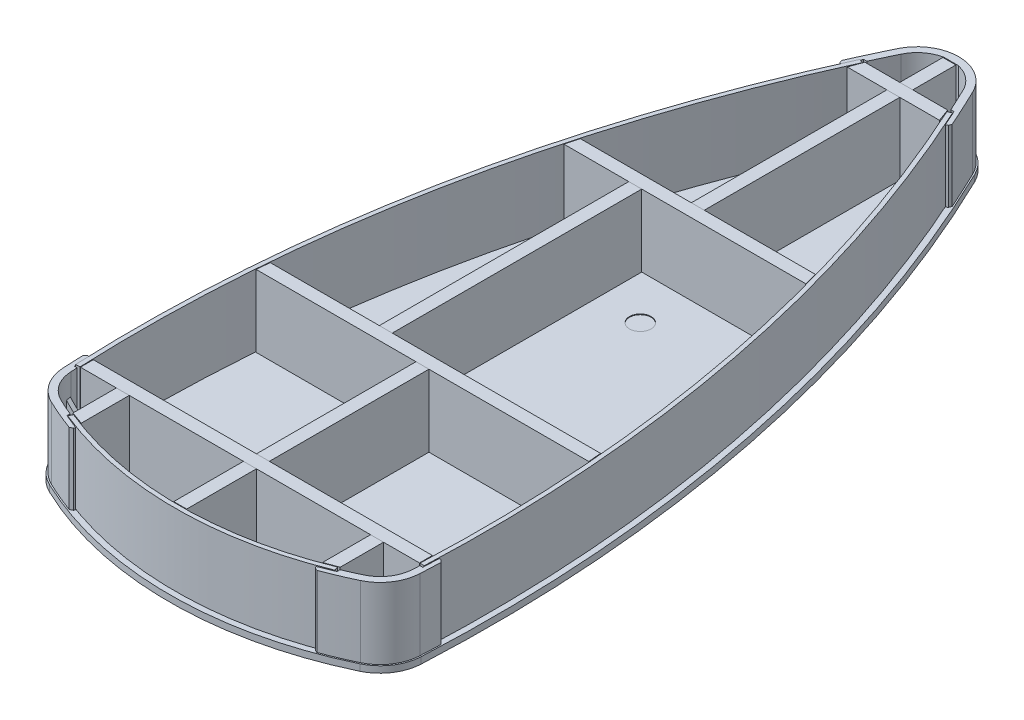
SolidWorks part; units mm, degrees
ref_plane "Front Plane" through (0, 0, 0) normal (0, 0, 1) x (1, 0, 0)
ref_plane "Top Plane" through (0, 0, 0) normal (0, 1, 0) x (1, 0, 0)
ref_plane "Right Plane" through (0, 0, 0) normal (1, 0, 0) x (0, 0, -1)
sketch "Sketch1" plane through (0, 0, 0) normal (0, 1, 0) x (1, 0, 0)
  line L0 (0, 550) -> (0, -550) construction
  arc A0 (-54.0521, 516.0455) -> (54.0521, 516.0455) centre (0, 490) cw
  arc A1 (-54.0521, 516.0455) -> (-249.9284, -449.7924) centre (1747.686, -352.1364) ccw
  arc A2 (-249.9284, -449.7924) -> (-215.9091, -500.9803) centre (-190, -446.8627) ccw
  arc A3 (-215.9091, -500.9803) -> (215.9091, -500.9803) centre (0, -50) ccw
  arc A4 (249.9284, -449.7924) -> (215.9091, -500.9803) centre (190, -446.8627) cw
  arc A5 (54.0521, 516.0455) -> (249.9284, -449.7924) centre (-1747.686, -352.1364) cw
  dimension "D1" = 500
  dimension "D2" = 500
  dimension "D4" = 2000
  dimension "D5" = 60
  dimension "D3" = 1100
extrude "Boss-Extrude1" add sketch "Sketch1" against normal blind 9
sketch "Sketch2" plane through (0, 0, 0) normal (0, 1, 0) x (1, 0, 0)
  line L0 (0, -120) -> (0, 105) construction
  circle A0 centre (0, 105) radius 15
  circle A1 centre (0, -120) radius 15
  dimension "D2" = 30
  dimension "D1" = 225
  dimension "D3" = 120
extrude "Cut-Extrude1" cut sketch "Sketch2" against normal blind 1
sketch "Sketch3" plane through (0, 0, 0) normal (0, 1, 0) x (1, 0, 0)
  line L0 (0, 475) -> (0, 0) construction
  line L1 (-9, 535) -> (9, 535)
  line L2 (-9, 535) -> (-9, 475)
  line L3 (-9, 475) -> (9, 475)
  line L4 (9, 535) -> (9, 475)
  line L5 (0, 550) -> (0, 535) construction
  arc A1 (54.0521, 516.0455) -> (-54.0521, 516.0455) centre (0, 490) ccw construction
  dimension "D1" = 18
  dimension "D2" = 15
  dimension "D3" = 60
extrude "Boss-Extrude2" add sketch "Sketch3" along normal blind 100 separate body
sketch "Sketch4" plane through (0, 0, 0) normal (0, 1, 0) x (1, 0, 0)
  line L0 (0, -180) -> (0, -198) construction
  line L1 (-57.642, 475) -> (57.642, 475)
  line L2 (-57.642, 475) -> (-64.1934, 457)
  line L3 (-64.1934, 457) -> (64.1934, 457)
  line L4 (57.642, 475) -> (64.1934, 457)
  line L5 (-9, 475) -> (9, 475) construction
  line L6 (0, 475) -> (0, 457) construction
  line L7 (9, 535) -> (-9, 535) construction
  line L8 (0, 535) -> (0, 550) construction
  line L9 (60.9177, 466) -> (75.0131, 471.1303) construction
  line L10 (0, 9) -> (0, 457) construction
  line L11 (-229.8118, -180) -> (229.8118, -180)
  line L12 (-229.8118, -180) -> (-231.3866, -198)
  line L13 (-231.3866, -198) -> (231.3866, -198)
  line L14 (229.8118, -180) -> (231.3866, -198)
  line L15 (230.5992, -189) -> (245.5421, -187.6927) construction
  line L16 (0, 9) -> (0, -9) construction
  line L17 (0, -550) -> (0, -493.7862) construction
  line L18 (0, -438) -> (0, -420) construction
  line L19 (-235.8365, -420) -> (235.8365, -420)
  line L20 (-235.8365, -420) -> (-235.8365, -438)
  line L21 (-235.8365, -438) -> (235.8365, -438)
  line L22 (235.8365, -420) -> (235.8365, -438)
  line L23 (0, -420) -> (0, 0) construction
  line L24 (235.8365, -429) -> (250.8365, -429) construction
  line L25 (0, 185) -> (0, 167) construction
  line L26 (-163.3545, 185) -> (163.3545, 185)
  line L27 (-163.3545, 185) -> (-168.1776, 167)
  line L28 (-168.1776, 167) -> (168.1776, 167)
  line L29 (163.3545, 185) -> (168.1776, 167)
  line L30 (165.766, 176) -> (180.2549, 179.8823) construction
  arc A0 (54.0521, 516.0455) -> (-54.0521, 516.0455) centre (0, 490) ccw construction
  arc A1 (249.9284, -449.7924) -> (54.0521, 516.0455) centre (-1747.686, -352.1364) ccw construction
  arc A2 (-215.9091, -500.9803) -> (215.9091, -500.9803) centre (0, -50) ccw construction
  dimension "D1" = 70
  dimension "D2" = 85
  dimension "D3" = 420
  dimension "D4" = 240
  dimension "D5" = 105
  dimension "D6" = 290
extrude "Boss-Extrude3" add sketch "Sketch4" along normal up to surface (100 mm away) separate body up to face at (0, 100, -505)
sketch "Sketch5" plane through (0, 0, 0) normal (0, 1, 0) x (1, 0, 0)
  line L0 (-235.8365, -438) -> (235.8365, -438) construction
  line L1 (-185.8365, -438) -> (-167.8365, -438)
  line L2 (-185.8365, -438) -> (-185.8365, -498.3413)
  line L3 (-185.8365, -498.3413) -> (-167.8365, -504.8928)
  line L4 (-167.8365, -438) -> (-167.8365, -504.8928)
  line L5 (-235.8365, -420) -> (-235.8365, -438) construction
  line L6 (167.8365, -438) -> (185.8365, -438)
  line L7 (167.8365, -438) -> (167.8365, -504.8928)
  line L8 (167.8365, -504.8928) -> (185.8365, -498.3413)
  line L9 (185.8365, -438) -> (185.8365, -498.3413)
  line L10 (-185.8365, -438) -> (-235.8365, -438) construction
  line L11 (185.8365, -438) -> (235.8365, -438) construction
  line L12 (-176.8365, -501.6171) -> (-181.9668, -515.7125) construction
  line L13 (0, 535) -> (0, 550) construction
  line L14 (9, 535) -> (-9, 535) construction
  line L15 (0, -535) -> (0, -550) construction
  line L16 (-9, -438) -> (9, -438)
  line L17 (-9, -438) -> (-9, -535)
  line L18 (-9, -535) -> (9, -535)
  line L19 (9, -438) -> (9, -535)
  line L20 (-231.3866, -198) -> (231.3866, -198) construction
  line L21 (-9, -198) -> (9, -198)
  line L22 (-9, -198) -> (-9, -420)
  line L23 (-9, -420) -> (9, -420)
  line L24 (9, -198) -> (9, -420)
  line L25 (235.8365, -420) -> (-235.8365, -420) construction
  line L26 (-64.1934, 457) -> (64.1934, 457) construction
  line L27 (-9, 457) -> (9, 457)
  line L28 (-9, 457) -> (-9, 185)
  line L29 (-9, 185) -> (9, 185)
  line L30 (9, 457) -> (9, 185)
  line L31 (9, 475) -> (9, 535) construction
  line L32 (163.3545, 185) -> (-163.3545, 185) construction
  line L33 (-9, 535) -> (-9, 475) construction
  line L34 (-168.1776, 167) -> (168.1776, 167) construction
  line L35 (-78, 167) -> (-60, 167)
  line L36 (-78, 167) -> (-78, -180)
  line L37 (-78, -180) -> (-60, -180)
  line L38 (-60, 167) -> (-60, -180)
  line L39 (229.8118, -180) -> (-229.8118, -180) construction
  arc A0 (-215.9091, -500.9803) -> (215.9091, -500.9803) centre (0, -50) ccw construction
  arc A1 (54.0521, 516.0455) -> (-54.0521, 516.0455) centre (0, 490) ccw construction
  dimension "D1" = 70
  dimension "D2" = 50
  dimension "D3" = 60
extrude "Boss-Extrude4" add sketch "Sketch5" along normal up to surface (100 mm away) separate body up to face at (0, 100, 429)
sketch "Sketch6" plane through (0, 0, 0) normal (0, 1, 0) x (1, 0, 0)
  line L0 (57.642, 475) -> (-57.642, 475) construction
  line L1 (-235.8365, -438) -> (235.8365, -438) construction
  line L2 (185.8365, -498.3413) -> (185.8365, -438) construction
  line L3 (-185.8365, -438) -> (-185.8365, -498.3413) construction
  arc A12 (-46.8452, 512.5727) -> (-241.938, -449.4018) centre (1747.686, -352.1364) ccw
  arc A13 (-241.938, -449.4018) -> (-212.4545, -493.7647) centre (-190, -446.8627) ccw
  arc A14 (-212.4545, -493.7647) -> (212.4545, -493.7647) centre (0, -50) ccw
  arc A15 (212.4545, -493.7647) -> (241.938, -449.4018) centre (190, -446.8627) ccw
  arc A16 (241.938, -449.4018) -> (46.8452, 512.5727) centre (-1747.686, -352.1364) ccw
  arc A17 (46.8452, 512.5727) -> (-46.8452, 512.5727) centre (0, 490) ccw
  arc A18 (-64.47, 475) -> (-242.4626, -438) centre (1747.686, -352.1364) ccw
  arc A20 (-185.8365, -505.5533) -> (185.8365, -505.5533) centre (0, -50) ccw
  arc A22 (242.4626, -438) -> (64.47, 475) centre (-1747.686, -352.1364) ccw
  dimension "D1" = 8
extrude "Extrude-Thin1" add sketch "Sketch6" along normal up to surface (100 mm away) separate body thin contours A18 | A22 | A20 up to face at (0, 100, 429) thin type one direction reverse wall 6
sketch "Sketch7" plane through (0, 0, 0) normal (0, 1, 0) x (1, 0, 0)
  line L0 (-64.47, 475) -> (-72.6832, 456.7642)
  line L1 (-64.47, 475) -> (-59.0117, 472.5086) construction
  line L2 (-72.6832, 456.7642) -> (-78.154, 459.2282)
  line L3 (-9, 535) -> (-9, 475) construction
  line L4 (0, 535) -> (0, 548) construction
  line L5 (9, 535) -> (-9, 535) construction
  line L6 (-64.47, 475) -> (-62.8274, 478.6472)
  line L7 (11, 537) -> (-11, 537)
  line L8 (-11, 537) -> (-11, 536.7226)
  line L9 (-62.8274, 478.6472) -> (-58.3989, 478.6472)
  line L10 (62.8274, 478.6472) -> (58.3989, 478.6472)
  line L11 (11, 537) -> (11, 536.7226)
  line L12 (64.47, 475) -> (62.8274, 478.6472)
  line L13 (72.6832, 456.7642) -> (78.154, 459.2282)
  line L14 (64.47, 475) -> (72.6832, 456.7642)
  arc A0 (-64.47, 475) -> (-242.4626, -438) centre (1747.686, -352.1364) ccw construction
  arc A1 (-78.154, 459.2282) -> (-52.2504, 515.1773) centre (1747.686, -352.1364) cw
  arc A2 (-52.2504, 515.1773) -> (52.2504, 515.1773) centre (0, 490) cw
  arc A3 (54.0521, 516.0455) -> (-54.0521, 516.0455) centre (0, 490) ccw construction
  arc A4 (-54.0521, 516.0455) -> (-249.9284, -449.7924) centre (1747.686, -352.1364) ccw construction
  arc A5 (-58.3989, 478.6472) -> (-43.2417, 510.8364) centre (1747.686, -352.1364) cw
  arc A6 (-43.2417, 510.8364) -> (-11, 536.7226) centre (0, 490) cw
  arc A7 (43.2417, 510.8364) -> (11, 536.7226) centre (0, 490) ccw
  arc A8 (58.3989, 478.6472) -> (43.2417, 510.8364) centre (-1747.686, -352.1364) ccw
  arc A9 (78.154, 459.2282) -> (52.2504, 515.1773) centre (-1747.686, -352.1364) ccw
  point P39 (0, 537)
  dimension "D2" = 2
  dimension "D4" = 2
  dimension "D6" = 10
  dimension "D1" = 20
  dimension "D3" = 2
  dimension "D5" = 4
extrude "Boss-Extrude5" add sketch "Sketch7" along normal offset from surface (99 mm away) 1 separate body up to face at (0, 100, -466)
chamfer "Chamfer1" distance 3 angle 45 2 edges at (78.154, 49.5, -459.2282) (-78.154, 49.5, -459.2282) first distance on face at (75.4186, 49.5, -457.9962) first distance on face at (-65.3101, 49.5, -487.2527)
sketch "Sketch9" plane through (0, 99, 0) normal (0, 1, 0) x (1, 0, 0)
  line L0 (0, 537) -> (0, 518.3881) construction
  line L1 (-20, 533.6348) -> (-26, 533.6348)
  line L2 (-20, 533.6348) -> (-20, 520.3485)
  line L3 (-20, 520.3485) -> (-26, 520.3485)
  line L4 (-26, 533.6348) -> (-26, 520.3485)
  line L5 (-11, 537) -> (11, 537) construction
  line L6 (26, 533.6348) -> (26, 520.3485)
  line L7 (20, 520.3485) -> (26, 520.3485)
  line L8 (20, 533.6348) -> (20, 520.3485)
  line L9 (20, 533.6348) -> (26, 533.6348)
  line L10 (-26, 530.3485) -> (-23.2349, 530.3485) construction
  arc A1 (-11, 536.7226) -> (-43.2417, 510.8364) centre (0, 490) ccw construction
  dimension "D1" = 10
  dimension "D2" = 6
  dimension "D3" = 40
extrude "Boss-Extrude9" add sketch "Sketch9" against normal mid plane 40 from offset 50 offset against normal yes
chamfer "Chamfer3" distance 13 angle 45 4 edges at (23, 29, -520.3485) (23, 69, -520.3485) (-23, 29, -520.3485) (-23, 69, -520.3485)
sketch "Sketch10" plane through (-26, 0, 0) normal (-1, 0, 0) x (0, 0, 1)
  line L0 (-530.3485, 32) -> (-530.3485, 66) construction
  line L1 (-530.3485, 44) -> (-526.3485, 44)
  line L2 (-530.3485, 44) -> (-530.3485, 54)
  line L3 (-530.3485, 54) -> (-526.3485, 54)
  line L4 (-526.3485, 44) -> (-526.3485, 54)
  line L5 (-526.3485, 49) -> (-520.3485, 49) construction
  line L6 (-520.3485, 42) -> (-520.3485, 56) construction
  dimension "D1" = 10
  dimension "D2" = 4
extrude "Cut-Extrude2" cut sketch "Sketch10" against normal up to surface (52 mm away) up to face at (26, 49, -525.3485)
sketch "Sketch8" plane through (0, 0, 0) normal (0, 1, 0) x (1, 0, 0)
  line L0 (-242.4626, -438) -> (-243.2244, -418.0145)
  line L1 (-243.2244, -418.0145) -> (-249.2201, -418.243)
  line L2 (-185.8365, -505.5533) -> (-167.3181, -513.1076)
  line L3 (-167.3181, -513.1076) -> (-169.4326, -518.2911)
  line L4 (-185.8365, -505.5533) -> (-183.5702, -499.9978) construction
  line L5 (-185.8365, -505.5533) -> (-187.8365, -504.7374)
  line L6 (-187.8365, -504.7374) -> (-187.8365, -500.4014)
  line L7 (-242.4626, -438) -> (-242.4626, -440)
  line L8 (-242.4626, -440) -> (-238.3714, -440)
  line L9 (-185.8365, -438) -> (-185.8365, -498.3413) construction
  line L10 (-235.8365, -438) -> (235.8365, -438) construction
  line L11 (0, 0) -> (0, -779.8531) construction
  arc A0 (-64.47, 475) -> (-242.4626, -438) centre (1747.686, -352.1364) ccw construction
  arc A1 (-249.2201, -418.243) -> (-247.9308, -449.6947) centre (1747.686, -352.1364) ccw
  arc A2 (-54.0521, 516.0455) -> (-249.9284, -449.7924) centre (1747.686, -352.1364) ccw construction
  arc A3 (-215.0455, -499.1764) -> (-247.9308, -449.6947) centre (-190, -446.8627) cw
  arc A4 (-249.9284, -449.7924) -> (-215.9091, -500.9803) centre (-190, -446.8627) ccw construction
  arc A6 (-215.0455, -499.1764) -> (-169.4326, -518.2911) centre (0, -50) ccw
  arc A8 (-215.9091, -500.9803) -> (215.9091, -500.9803) centre (0, -50) ccw construction
  arc A12 (-185.8365, -505.5533) -> (185.8365, -505.5533) centre (0, -50) ccw construction
  arc A13 (-238.3714, -440) -> (-237.9427, -449.2064) centre (1747.686, -352.1364) ccw
  arc A14 (-237.9427, -449.2064) -> (-210.7273, -490.1568) centre (-190, -446.8627) ccw
  arc A15 (-210.7273, -490.1568) -> (-187.8365, -500.4014) centre (0, -50) ccw
  dimension "D1" = 2
  dimension "D2" = 2
  dimension "D6" = 10
  dimension "D3" = 2
  dimension "D4" = 20
  dimension "D5" = 20
extrude "Boss-Extrude8" add sketch "Sketch8" along normal up to surface (99 mm away) separate body contours A15 A14 A13 L8 L7 L0 L1 A1 A3 A6 L3 L2 L5 L6 region at (-243.7574, 0, 439) up to face at (0.0004, 99, -494.883)
chamfer "Chamfer2" distance 3 angle 45 2 edges at (-249.2201, 49.5, 418.243) (-169.4326, 49.5, 518.2911) first distance on face at (-246.2223, 49.5, 418.1288) first distance on face at (-192.3577, 49.5, 509.0171)
sketch "Sketch11" plane through (0, 99, 0) normal (0, 1, 0) x (1, 0, 0)
  line L0 (-235.8365, -438) -> (235.8365, -438) construction
  line L1 (-237.9038, -450) -> (-225.9038, -450)
  line L2 (-237.9038, -450) -> (-237.9038, -456)
  line L3 (-237.9038, -456) -> (-225.9038, -456)
  line L4 (-225.9038, -450) -> (-225.9038, -456)
  line L5 (-197.8365, -496.0995) -> (-203.8365, -496.0995)
  line L6 (-197.8365, -496.0995) -> (-197.8365, -484.0995)
  line L7 (-197.8365, -484.0995) -> (-203.8365, -484.0995)
  line L8 (-203.8365, -496.0995) -> (-203.8365, -484.0995)
  line L9 (-185.8365, -438) -> (-185.8365, -498.3413) construction
  arc A0 (-238.3714, -440) -> (-237.9427, -449.2064) centre (1747.686, -352.1364) ccw construction
  arc A1 (-210.7273, -490.1568) -> (-187.8365, -500.4014) centre (0, -50) ccw construction
  dimension "D1" = 6
  dimension "D2" = 12
  dimension "D3" = 12
  dimension "D4" = 12
  dimension "D5" = 12
extrude "Boss-Extrude10" add sketch "Sketch11" along normal mid plane 40 from offset 50 offset against normal yes
chamfer "Chamfer4" distance 12 angle 45 4 edges at (-200.8365, 29, 484.0995) (-200.8365, 69, 484.0995) (-225.9038, 29, 453) (-225.9038, 69, 453)
sketch "Sketch12" plane through (0, 0, 456) normal (0, 0, 1) x (1, 0, 0)
  line L0 (-237.1223, 29.7815) -> (-237.1223, 68.2185) construction
  line L1 (-237.1223, 54) -> (-233.1223, 54)
  line L2 (-237.1223, 54) -> (-237.1223, 44)
  line L3 (-237.1223, 44) -> (-233.1223, 44)
  line L4 (-233.1223, 54) -> (-233.1223, 44)
  line L5 (-233.1223, 49) -> (-225.9038, 49) construction
  line L6 (-225.9038, 57) -> (-225.9038, 41) construction
  dimension "D1" = 10
  dimension "D2" = 4
extrude "Cut-Extrude3" cut sketch "Sketch12" against normal up to next (6 mm away)
sketch "Sketch13" plane through (-203.8365, 0, 0) normal (-1, 0, 0) x (0, 0, 1)
  line L0 (493.39, 66.2905) -> (493.39, 31.7095) construction
  line L1 (493.39, 44) -> (489.39, 44)
  line L2 (493.39, 44) -> (493.39, 54)
  line L3 (493.39, 54) -> (489.39, 54)
  line L4 (489.39, 44) -> (489.39, 54)
  line L5 (489.39, 49) -> (484.0995, 49) construction
  line L6 (484.0995, 57) -> (484.0995, 41) construction
  dimension "D1" = 10
  dimension "D2" = 4
extrude "Cut-Extrude4" cut sketch "Sketch13" against normal up to next (6 mm away)
mirror "Mirror1" about plane through (0, 0, 0) normal (1, 0, 0) of bodies 125 119
